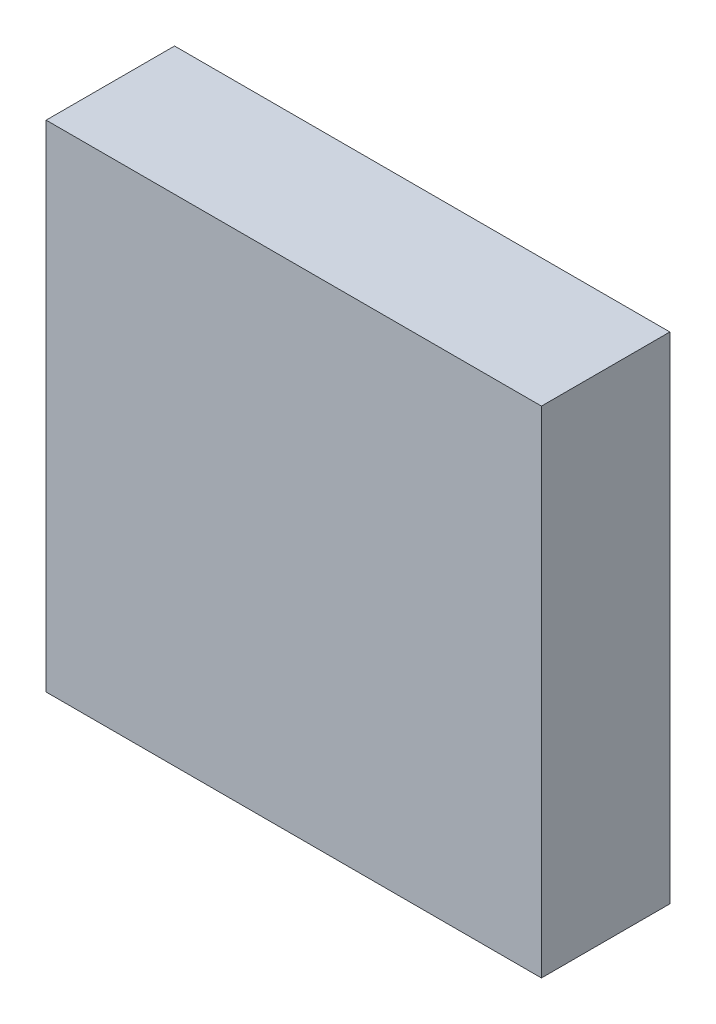
SolidWorks part; units mm, degrees
ref_plane "Ebene vorne" through (0, 0, 0) normal (0, 0, 1) x (1, 0, 0)
ref_plane "Ebene oben" through (0, 0, 0) normal (0, 1, 0) x (1, 0, 0)
ref_plane "Ebene rechts" through (0, 0, 0) normal (1, 0, 0) x (0, 0, -1)
sketch "Skizze1" plane through (0, 0, 0) normal (0, 0, 1) x (1, 0, 0)
  line L0 (67.5, 67.5) -> (-67.5, 67.5) construction
  line L1 (-67.5, 67.5) -> (-67.5, -67.5) construction
  line L2 (67.5, -67.5) -> (67.5, 67.5) construction
  line L3 (-67.5, -67.5) -> (67.5, -67.5) construction
  line L4 (67.5, 67.5) -> (-67.5, 67.5)
  line L5 (-67.5, 67.5) -> (-67.5, -67.5)
  line L6 (67.5, -67.5) -> (67.5, 67.5)
  line L7 (-67.5, -67.5) -> (67.5, -67.5)
  line L8 (62.5, 62.5) -> (-62.5, 62.5)
  line L9 (-62.5, 62.5) -> (-62.5, -62.5)
  line L10 (-62.5, -62.5) -> (62.5, -62.5)
  line L11 (62.5, -62.5) -> (62.5, 62.5)
  dimension "D1" = 5
extrude "Aufsatz-Linear austragen1" add sketch "Skizze1" along normal blind 30
sketch "Skizze2" plane through (0, 0, 30) normal (0, 0, 1) x (1, 0, 0)
  line L0 (-67.5, 67.5) -> (-67.5, -67.5) construction
  line L1 (-67.5, -67.5) -> (67.5, -67.5) construction
  line L2 (67.5, -67.5) -> (67.5, 67.5) construction
  line L3 (67.5, 67.5) -> (-67.5, 67.5) construction
  line L4 (-67.5, 67.5) -> (-67.5, -67.5)
  line L5 (-67.5, -67.5) -> (67.5, -67.5)
  line L6 (67.5, -67.5) -> (67.5, 67.5)
  line L7 (67.5, 67.5) -> (-67.5, 67.5)
extrude "Aufsatz-Linear austragen2" add sketch "Skizze2" along normal blind 5
